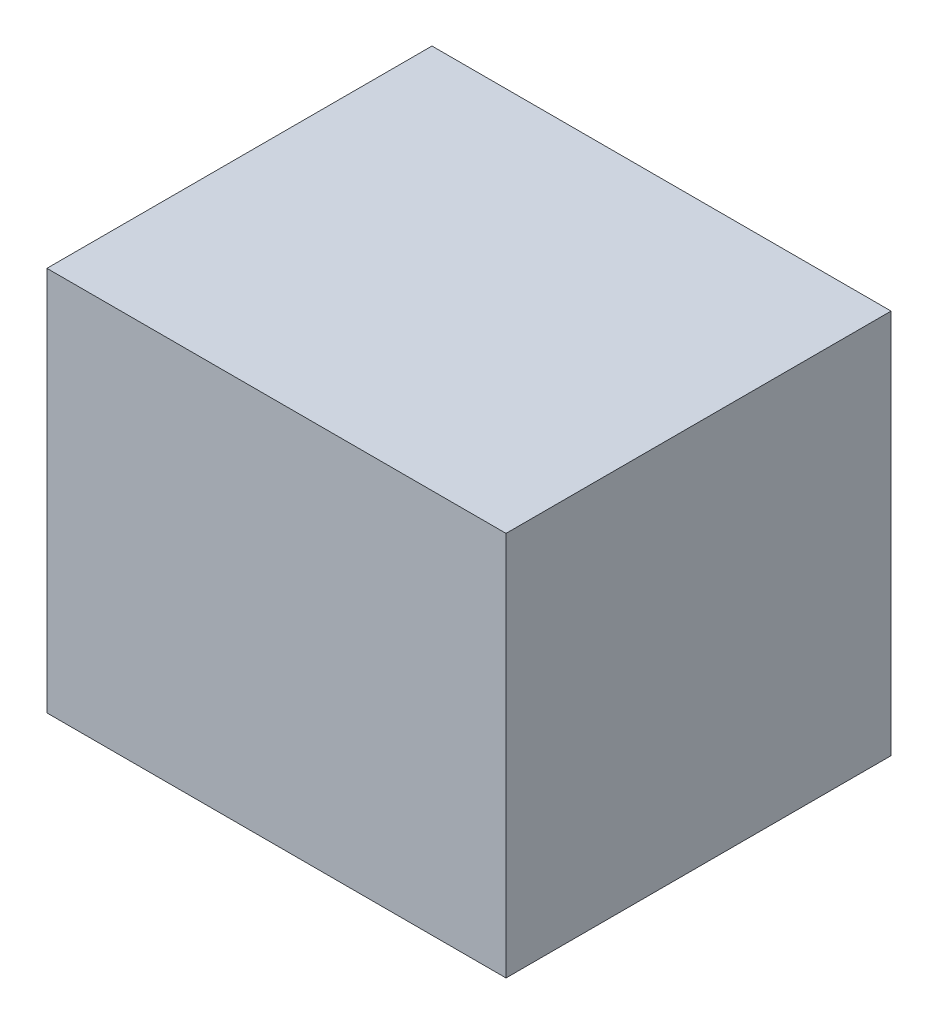
SolidWorks part; units mm, degrees
ref_plane "Ebene vorne" through (0, 0, 0) normal (0, 0, 1) x (1, 0, 0)
ref_plane "Ebene oben" through (0, 0, 0) normal (0, 1, 0) x (1, 0, 0)
ref_plane "Ebene rechts" through (0, 0, 0) normal (1, 0, 0) x (0, 0, -1)
sketch "Skizze1" plane through (0, 0, 0) normal (0, 0, 1) x (1, 0, 0)
  line L1 (-38.75, -32.5) -> (38.75, -32.5)
  line L2 (-38.75, -32.5) -> (-38.75, 32.5)
  line L3 (-38.75, 32.5) -> (38.75, 32.5)
  line L4 (38.75, -32.5) -> (38.75, 32.5)
  line L5 (-38.75, -32.5) -> (38.75, 32.5) construction
  line L6 (-38.75, 32.5) -> (38.75, -32.5) construction
  point P0 (0, 0)
  dimension "D1" = 65
  dimension "D2" = 77.5
extrude "Aufsatz-Linear austragen1" add sketch "Skizze1" along normal blind 65
